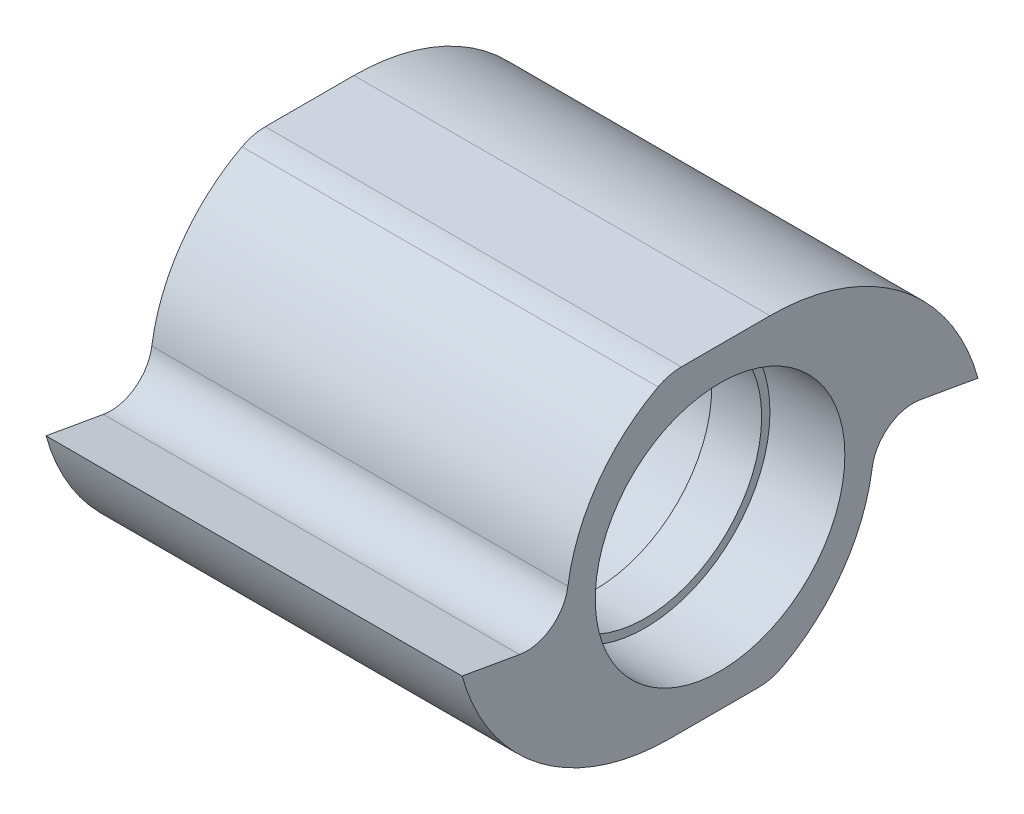
SolidWorks part; units mm, degrees
material "AISI 4340 Steel, annealed"
ref_plane "Front Plane" through (0, 0, 0) normal (0, 0, 1) x (1, 0, 0)
ref_plane "Top Plane" through (0, 0, 0) normal (0, 1, 0) x (1, 0, 0)
ref_plane "Right Plane" through (0, 0, 0) normal (1, 0, 0) x (0, 0, -1)
other "Center of Mass"
ref_axis "Axis1" through (-27.5, 0, 0) along (1, 0, 0)
sketch "Sketch1" plane through (0, 0, 0) normal (1, 0, 0) x (0, 0, -1)
  line L3 (-31, 0) -> (31, 0) construction
  line L4 (-31, 0) -> (-18.3654, -2.2278)
  line L6 (-18.5, 0) -> (18.5, 0)
  line L7 (6, -19) -> (-6, -19)
  line L9 (0, -19) -> (0, 0) construction
  line L12 (31, -19) -> (-31, -19) construction
  line L13 (31, -19) -> (31, 19) construction
  line L14 (31, 19) -> (-31, 19) construction
  line L15 (-31, -19) -> (-31, 19) construction
  line L16 (31, -19) -> (-31, 19) construction
  line L17 (31, 19) -> (-31, -19) construction
  circle A4 centre (0, 0) radius 31 construction
  circle A5 centre (0, 0) radius 18.5 construction
  arc A7 (-18.3654, -2.2278) -> (-18.5, 0) centre (0, 0) cw
  arc A8 (-31, 0) -> (-6, -19) centre (-6, 6.9474) ccw
  arc A10 (18.5, 0) -> (6, -19) centre (-2.19, 0) cw
  dimension "D1" = 62
  dimension "D3" = 37
  dimension "D4" = 38
  dimension "D2" = 10
  dimension "D5" = 12
extrude "Boss-Extrude1" add sketch "Sketch1" along normal mid plane 50
fillet "Fillet2" radius 6 1 edges at (0, -19, -6)
pattern_circular "CirPattern1" count 2 over 360 about axis through (-27.5, 0, 0) along (1, 0, 0) of "Boss-Extrude1", "Fillet2"
fillet "Fillet1" radius 5 2 edges at (0, 2.2278, -18.3654) (0, -2.2278, 18.3654)
sketch "Sketch4" plane through (25, 0, 0) normal (1, 0, 0) x (0, 0, -1)
  circle A0 centre (0, 0) radius 14
  point P2 (0, 0)
  point P3 (0, 0)
  point P4 (0, 0)
  dimension "D1" = 28
extrude "Cut-Extrude1" cut sketch "Sketch4" against normal through all
sketch "Sketch5" plane through (-25, 0, 0) normal (-1, 0, 0) x (0, 0, 1)
  circle A0 centre (0, 0) radius 17.5
  circle A1 centre (0, 0) radius 14 construction
  dimension "D1" = 35
extrude "Cut-Extrude2" cut sketch "Sketch5" against normal blind 25
sketch "Sketch6" plane through (0, 0, 0) normal (-1, 0, 0) x (0, 0, 1)
  circle A0 centre (0, 0) radius 15
  circle A1 centre (0, 0) radius 14 construction
  dimension "D1" = 30
extrude "Cut-Extrude3" cut sketch "Sketch6" against normal blind 10
sketch "Sketch7" plane through (25, 0, 0) normal (1, 0, 0) x (0, 0, -1)
  circle A0 centre (0, 0) radius 15
  circle A1 centre (0, 0) radius 14 construction
  dimension "D1" = 30
extrude "Cut-Extrude4" cut sketch "Sketch7" against normal blind 9
